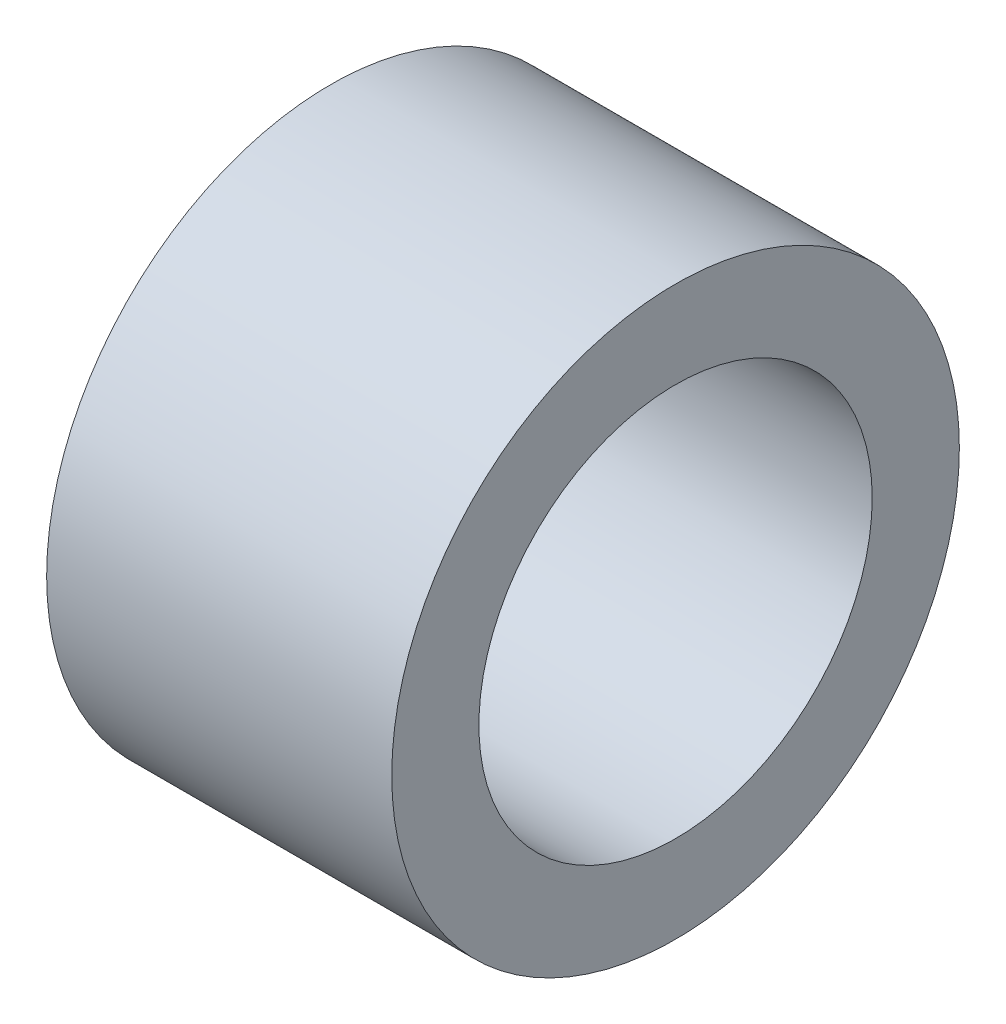
SolidWorks part; units mm, degrees
material "Brass"
ref_plane "Front Plane" through (0, 0, 0) normal (1, 0, 0) x (0, 1, 0)
ref_plane "Top Plane" through (0, 0, 0) normal (0, 0, 1) x (0, 1, 0)
ref_plane "Right Plane" through (0, 0, 0) normal (0, 1, 0) x (-1, 0, 0)
sketch "Sketch1" plane through (0, 0, 0) normal (1, 0, 0) x (0, 1, 0)
  circle A0 centre (0, 0) radius 5.5
  circle A1 centre (0, 0) radius 7.9375
  dimension "D1" = 11
  dimension "D2" = 15.875
extrude "Boss-Extrude1" add sketch "Sketch1" along normal blind 9.652
equation "\"D1@Sketch1\"=11mm"
